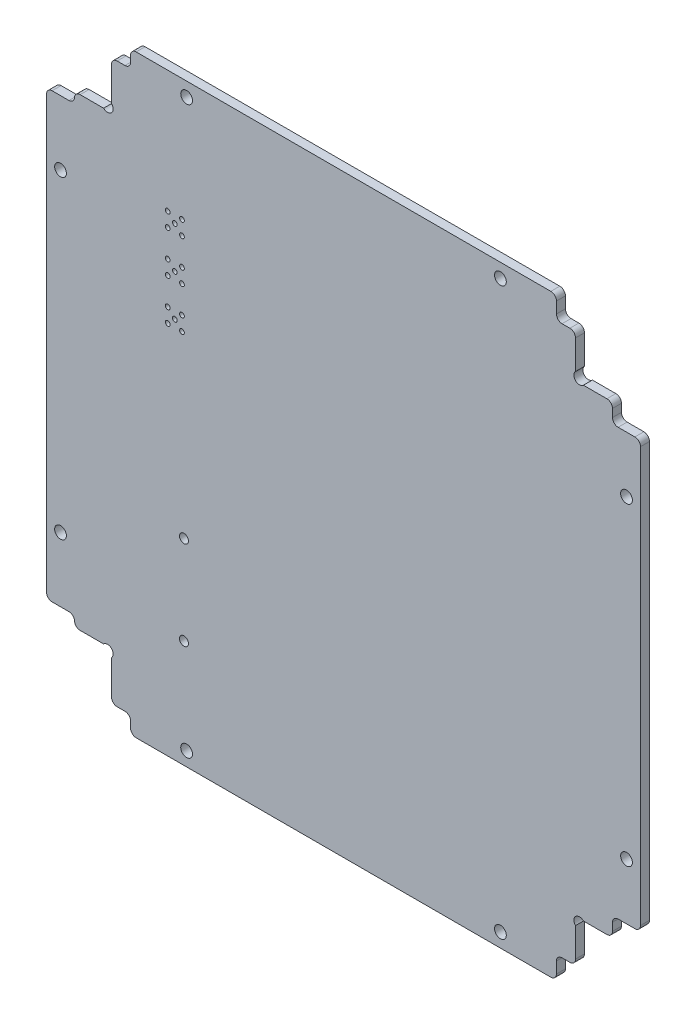
SolidWorks part; units mm, degrees
ref_plane "Front Plane" through (0, 0, 0) normal (0, 0, 1) x (1, 0, 0)
ref_plane "Top Plane" through (0, 0, 0) normal (0, 1, 0) x (1, 0, 0)
ref_plane "Right Plane" through (0, 0, 0) normal (1, 0, 0) x (0, 0, -1)
sketch "Sketch1" plane through (0, 0, 0) normal (0, 0, 1) x (1, 0, 0)
  line L0 (53, 53) -> (-53, -53) construction
  line L1 (53, 53) -> (-53, 53)
  line L2 (53, 53) -> (53, -53)
  line L3 (53, -53) -> (-53, -53)
  line L4 (-53, 53) -> (-53, -53)
  point P4 (0, 0)
  dimension "D1" = 106
  dimension "D2" = 106
extrude "mainOutline" add sketch "Sketch1" along normal blind 1.6
sketch "axisLabels" plane through (0, 0, 0) normal (0, 0, -1) x (-1, 0, 0)
  text T0 "+Y"
  text T1 "+X"
sketch "Sketch4" plane through (0, 0, 0) normal (0, 0, -1) x (-1, 0, 0)
  line L1 (-41.4, -41.4) -> (-48, -41.4)
  line L3 (-41.4, -49) -> (-41.4, -41.4)
  line L5 (-60.1065, -39) -> (-49.9975, -39)
  line L7 (-39, -61.4521) -> (-39, -49.9)
  line L9 (39, -56.2753) -> (39, -49.9)
  line L10 (-53, 53) -> (53, 53) construction
  line L11 (41.4, -49.9) -> (41.4, -41.4)
  line L12 (-53, -53) -> (-53, 53) construction
  line L13 (41.4, -41.4) -> (48, -41.4)
  line L15 (48, -40.5) -> (55.5177, -40.5)
  line L17 (55.3838, 40.5) -> (48, 40.5)
  line L19 (39, 57.6877) -> (39, 49.9)
  line L21 (-39, 59.8804) -> (-39, 49.9)
  line L23 (-56.8428, 39) -> (-49.9975, 39)
  line L25 (-41.4, 41.4) -> (-41.4, 49)
  line L27 (-48, 41.4) -> (-41.4, 41.4)
  line L29 (41.4, 49.9) -> (41.4, 41.4)
  line L31 (48, 41.4) -> (41.4, 41.4)
  line L32 (-48, 41.4) -> (-48, 39)
  line L33 (-48, 39) -> (-49.9975, 39)
  line L34 (-41.4, 49) -> (-39, 49)
  line L35 (-39, 49) -> (-39, 49.9)
  line L36 (48, 40.5) -> (48, 41.4)
  line L37 (39, 49.9) -> (41.4, 49.9)
  line L38 (48, -40.5) -> (48, -41.4)
  line L39 (39, -49.9) -> (41.4, -49.9)
  line L40 (-41.4, -49) -> (-39, -49)
  line L41 (-39, -49) -> (-39, -49.9)
  line L42 (-49.9975, -39) -> (-48, -39)
  line L43 (-48, -39) -> (-48, -41.4)
  line L44 (-39, 59.8804) -> (-56.8428, 59.8804)
  line L45 (-56.8428, 59.8804) -> (-56.8428, 39)
  line L46 (53, 53) -> (53, -53) construction
  line L47 (-60.1065, -39) -> (-60.1065, -61.4521)
  line L48 (-60.1065, -61.4521) -> (-39, -61.4521)
  line L49 (39, -56.2753) -> (55.5177, -56.2753)
  line L50 (55.5177, -56.2753) -> (55.5177, -40.5)
  line L51 (55.3838, 40.5) -> (55.3838, 57.6877)
  line L52 (55.3838, 57.6877) -> (39, 57.6877)
  line L53 (53, -53) -> (-53, -53) construction
  dimension "D1" = 14
  dimension "D2" = 11.6
  dimension "D3" = 5
  dimension "D4" = 12.5
  dimension "D5" = 11.6
  dimension "D6" = 3.1
  dimension "D7" = 12.5
  dimension "D8" = 14
  dimension "D9" = 3.1
  dimension "D10" = 5
  dimension "D11" = 11.6
  dimension "D12" = 11.6
  dimension "D13" = 14
  dimension "D14" = 14
  dimension "D15" = 11.6
  dimension "D16" = 11.6
  dimension "D17" = 5
  dimension "D18" = 4
  dimension "D19" = 14
  dimension "D20" = 14
  dimension "D21" = 11.6
  dimension "D22" = 11.6
  dimension "D23" = 4
  dimension "D24" = 5
extrude "railCutouts" cut sketch "Sketch4" against normal through all
sketch "Sketch5" plane through (0, 0, 0) normal (0, 0, -1) x (-1, 0, 0)
  line L0 (-48.7071, -39.7071) -> (-52.4015, -43.4015) construction
  line L1 (-48, -40.4142) -> (-51.6944, -44.1086) construction
  line L2 (-49.4142, -39) -> (-53.1086, -42.6944) construction
  line L3 (-48, -41.4) -> (-48, -39) construction
  line L4 (-48, 39) -> (-48, 41.4) construction
  line L5 (-42.1071, -42.1071) -> (-45.4445, -45.4445) construction
  line L6 (-41.4, -42.8142) -> (-44.7374, -46.1516)
  line L7 (-42.8142, -41.4) -> (-46.1516, -44.7374)
  line L8 (-39.7071, -49.7071) -> (-42.6199, -52.6199) construction
  line L9 (-39, -50.4142) -> (-41.9128, -53.327) construction
  line L10 (-40.4142, -49) -> (-43.327, -51.9128) construction
  line L11 (39.7071, -50.6071) -> (41.4231, -52.3231) construction
  line L12 (40.4142, -49.9) -> (42.1302, -51.616) construction
  line L13 (39, -51.3142) -> (40.716, -53.0302) construction
  line L14 (42.1071, -42.1071) -> (44.0402, -44.0402) construction
  line L15 (42.8142, -41.4) -> (44.7473, -43.3331)
  line L16 (41.4, -42.8142) -> (43.3331, -44.7473)
  line L17 (48.7071, -41.2071) -> (49.9793, -42.4793) construction
  line L18 (49.4142, -40.5) -> (50.6865, -41.7722) construction
  line L19 (48, -41.9142) -> (49.2722, -43.1865) construction
  line L20 (48.7071, 41.2071) -> (50.5001, 43.0001) construction
  line L21 (48, 41.9142) -> (49.793, 43.7072) construction
  line L22 (49.4142, 40.5) -> (51.2072, 42.293) construction
  line L23 (42.1071, 42.1071) -> (44.029, 44.029) construction
  line L24 (41.4, 42.8142) -> (43.3219, 44.7361)
  line L25 (42.8142, 41.4) -> (44.7361, 43.3219)
  line L26 (39.7071, 50.6071) -> (41.2638, 52.1638) construction
  line L27 (39, 51.3142) -> (40.5567, 52.8709) construction
  line L28 (40.4142, 49.9) -> (41.9709, 51.4567) construction
  line L29 (-48.7071, 39.7071) -> (-50.0606, 41.0606) construction
  line L30 (-49.4142, 39) -> (-50.7677, 40.3535) construction
  line L31 (-48, 40.4142) -> (-49.3535, 41.7677) construction
  line L32 (-42.1071, 42.1071) -> (-43.7968, 43.7968) construction
  line L33 (-42.8142, 41.4) -> (-44.5039, 43.0897)
  line L34 (-41.4, 42.8142) -> (-43.0897, 44.5039)
  line L35 (-39.7071, 49.7071) -> (-41.256, 51.256) construction
  line L36 (-40.4142, 49) -> (-41.9631, 50.5489) construction
  line L37 (-39, 50.4142) -> (-40.5489, 51.9631) construction
  line L38 (-41.4, 41.4) -> (-41.4, 49) construction
  line L39 (-39, 49) -> (-39, 53) construction
  line L40 (39, 53) -> (39, 49.9) construction
  line L41 (41.4, 49.9) -> (41.4, 41.4) construction
  line L42 (48, 41.4) -> (48, 40.5) construction
  line L43 (39, -49.9) -> (39, -53) construction
  line L44 (41.4, -41.4) -> (41.4, -49.9) construction
  line L45 (53, -40.5) -> (48, -40.5) construction
  line L46 (-39, -53) -> (-39, -49) construction
  line L47 (-41.4, -49) -> (-41.4, -41.4) construction
  arc A0 (-48, -40.4142) -> (-49.4142, -39) centre (-48.7071, -39.7071) ccw construction
  arc A1 (-53.1086, -42.6944) -> (-51.6944, -44.1086) centre (-52.4015, -43.4015) ccw construction
  arc A2 (-41.4, -42.8142) -> (-42.8142, -41.4) centre (-42.1071, -42.1071) ccw
  arc A3 (-46.1516, -44.7374) -> (-44.7374, -46.1516) centre (-45.4445, -45.4445) ccw
  arc A4 (-39, -50.4142) -> (-40.4142, -49) centre (-39.7071, -49.7071) ccw construction
  arc A5 (-43.327, -51.9128) -> (-41.9128, -53.327) centre (-42.6199, -52.6199) ccw construction
  arc A6 (40.4142, -49.9) -> (39, -51.3142) centre (39.7071, -50.6071) ccw construction
  arc A7 (40.716, -53.0302) -> (42.1302, -51.616) centre (41.4231, -52.3231) ccw construction
  arc A8 (42.8142, -41.4) -> (41.4, -42.8142) centre (42.1071, -42.1071) ccw
  arc A9 (43.3331, -44.7473) -> (44.7473, -43.3331) centre (44.0402, -44.0402) ccw
  arc A10 (49.4142, -40.5) -> (48, -41.9142) centre (48.7071, -41.2071) ccw construction
  arc A11 (49.2722, -43.1865) -> (50.6865, -41.7722) centre (49.9793, -42.4793) ccw construction
  arc A12 (48, 41.9142) -> (49.4142, 40.5) centre (48.7071, 41.2071) ccw construction
  arc A13 (51.2072, 42.293) -> (49.793, 43.7072) centre (50.5001, 43.0001) ccw construction
  arc A14 (41.4, 42.8142) -> (42.8142, 41.4) centre (42.1071, 42.1071) ccw
  arc A15 (44.7361, 43.3219) -> (43.3219, 44.7361) centre (44.029, 44.029) ccw
  arc A16 (39, 51.3142) -> (40.4142, 49.9) centre (39.7071, 50.6071) ccw construction
  arc A17 (41.9709, 51.4567) -> (40.5567, 52.8709) centre (41.2638, 52.1638) ccw construction
  arc A18 (-49.4142, 39) -> (-48, 40.4142) centre (-48.7071, 39.7071) ccw construction
  arc A19 (-49.3535, 41.7677) -> (-50.7677, 40.3535) centre (-50.0606, 41.0606) ccw construction
  arc A20 (-42.8142, 41.4) -> (-41.4, 42.8142) centre (-42.1071, 42.1071) ccw
  arc A21 (-43.0897, 44.5039) -> (-44.5039, 43.0897) centre (-43.7968, 43.7968) ccw
  arc A22 (-40.4142, 49) -> (-39, 50.4142) centre (-39.7071, 49.7071) ccw construction
  arc A23 (-40.5489, 51.9631) -> (-41.9631, 50.5489) centre (-41.256, 51.256) ccw construction
  point P2 (-50.5543, -41.5543)
  point P9 (-43.7758, -43.7758)
  point P17 (-41.1635, -51.1635)
  point P24 (40.5651, -51.4651)
  point P31 (43.0736, -43.0736)
  point P38 (49.3432, -41.8432)
  point P45 (49.6036, 42.1036)
  point P52 (43.0681, 43.0681)
  point P59 (40.4855, 51.3855)
  point P66 (-49.3839, 40.3839)
  point P73 (-42.952, 42.952)
  point P80 (-40.4815, 50.4815)
  dimension "D2" = 1
  dimension "D1" = 45
  dimension "D3" = 45
  dimension "D4" = 45
  dimension "D5" = 45
  dimension "D6" = 45
  dimension "D7" = 45
  dimension "D8" = 45
  dimension "D9" = 45
  dimension "D10" = 45
  dimension "D11" = 45
  dimension "D12" = 45
  dimension "D13" = 45
extrude "dogbones" cut sketch "Sketch5" against normal through all
sketch "Sketch6" plane through (0, 0, 0) normal (0, 0, -1) x (-1, 0, 0)
  line L0 (-39, 50) -> (-39, 53) construction
  line L1 (-39, 49) -> (-39, 53) construction
  line L2 (-39, 53) -> (39, 53) construction
  line L3 (-40, 50) -> (-40, 53)
  line L4 (-38, 50) -> (-38, 53)
  line L5 (-49, 39) -> (-53, 39) construction
  line L6 (-53, 39) -> (-48, 39) construction
  line L7 (-49, 38) -> (-53, 38)
  line L8 (-49, 40) -> (-53, 40)
  line L9 (-49, -39) -> (-55.2142, -39) construction
  line L10 (-48, -39) -> (-53, -39) construction
  line L11 (-49, -40) -> (-55.2142, -40)
  line L12 (-49, -38) -> (-55.2142, -38)
  line L13 (-39, -50) -> (-39, -53.9161) construction
  line L14 (-39, -53) -> (-39, -49) construction
  line L15 (-38, -50) -> (-38, -53.9161)
  line L16 (-40, -50) -> (-40, -53.9161)
  line L17 (39, -50.9) -> (39, -54.538) construction
  line L18 (39, -49.9) -> (39, -53) construction
  line L19 (40, -50.9) -> (40, -54.538)
  line L20 (38, -50.9) -> (38, -54.538)
  line L21 (49, -40.5) -> (54.2026, -40.5) construction
  line L22 (53, -40.5) -> (48, -40.5) construction
  line L23 (49, -39.5) -> (54.2026, -39.5)
  line L24 (49, -41.5) -> (54.2026, -41.5)
  line L25 (49, 40.5) -> (54.5566, 40.5) construction
  line L26 (48, 40.5) -> (53, 40.5) construction
  line L27 (49, 41.5) -> (54.5566, 41.5)
  line L28 (49, 39.5) -> (54.5566, 39.5)
  line L29 (39, 50.9) -> (39, 55.8281) construction
  line L30 (39, 53) -> (39, 49.9) construction
  line L31 (38, 50.9) -> (38, 55.8281)
  line L32 (40, 50.9) -> (40, 55.8281)
  line L33 (-48, -41.4) -> (-48, -39) construction
  line L34 (-39, -49) -> (-41.4, -49) construction
  line L35 (41.4, -49.9) -> (39, -49.9) construction
  line L36 (48, -40.5) -> (48, -41.4) construction
  line L37 (48, 41.4) -> (48, 40.5) construction
  line L38 (39, 49.9) -> (41.4, 49.9) construction
  arc A0 (-40, 50) -> (-38, 50) centre (-39, 50) ccw
  arc A1 (-38, 53) -> (-40, 53) centre (-39, 53) ccw
  arc A2 (-49, 38) -> (-49, 40) centre (-49, 39) ccw
  arc A3 (-53, 40) -> (-53, 38) centre (-53, 39) ccw
  arc A4 (-49, -40) -> (-49, -38) centre (-49, -39) ccw
  arc A5 (-55.2142, -38) -> (-55.2142, -40) centre (-55.2142, -39) ccw
  arc A6 (-38, -50) -> (-40, -50) centre (-39, -50) ccw
  arc A7 (-40, -53.9161) -> (-38, -53.9161) centre (-39, -53.9161) ccw
  arc A8 (40, -50.9) -> (38, -50.9) centre (39, -50.9) ccw
  arc A9 (38, -54.538) -> (40, -54.538) centre (39, -54.538) ccw
  arc A10 (49, -39.5) -> (49, -41.5) centre (49, -40.5) ccw
  arc A11 (54.2026, -41.5) -> (54.2026, -39.5) centre (54.2026, -40.5) ccw
  arc A12 (49, 41.5) -> (49, 39.5) centre (49, 40.5) ccw
  arc A13 (54.5566, 39.5) -> (54.5566, 41.5) centre (54.5566, 40.5) ccw
  arc A14 (38, 50.9) -> (40, 50.9) centre (39, 50.9) ccw
  arc A15 (40, 55.8281) -> (38, 55.8281) centre (39, 55.8281) ccw
  point P6 (-39, 51.5)
  point P11 (-51, 39)
  point P21 (-52.1071, -39)
  point P30 (-39, -51.958)
  point P39 (39, -52.719)
  point P48 (51.6013, -40.5)
  point P57 (51.7783, 40.5)
  point P66 (39, 53.364)
  point P75 (-39, 49)
  dimension "D1" = 1
extrude "solarFillets" cut sketch "Sketch6" against normal through all
fillet "handlingFillets" radius 1 16 edges at (-41.4, -49.9, 0.8) (-38, -53, 0.8) (-53, -39.5, 0.8) (-48, -41.4, 0.8) (-48, 41.4, 0.8) (-53, 39.5, 0.8) (-41.4, 49.9, 0.8) (-38, 53, 0.8) (38, 53, 0.8) (41.4, 49, 0.8) (48, 41.4, 0.8) (53, 38, 0.8) (53, -38, 0.8) (48, -41.4, 0.8) (41.4, -49, 0.8) (38, -53, 0.8)
sketch "Sketch7" plane through (0, 0, 1.6) normal (0, 0, 1) x (1, 0, 0)
  line L0 (-37, -53) -> (37, -53) construction
  line L1 (-53, 38.5) -> (-53, -38.5) construction
  line L2 (37, 53) -> (-37, 53) construction
  line L3 (-31.37, 28.67) -> (-31.37, 31.21) construction
  line L4 (-31.37, 31.21) -> (-28.83, 31.21) construction
  line L5 (-28.83, 31.21) -> (-28.83, 28.67) construction
  line L6 (-28.83, 28.67) -> (-31.37, 28.67) construction
  line L7 (-31.37, 28.67) -> (-28.83, 31.21) construction
  circle A1 centre (-28.4723, -17.925) radius 0.8
  circle A3 centre (-28.4723, -33.775) radius 0.8
  circle A5 centre (-31.37, 28.67) radius 0.425
  circle A7 centre (-28.83, 28.67) radius 0.425
  circle A9 centre (-30.1, 29.94) radius 0.425
  circle A10 centre (-28.83, 31.21) radius 0.425
  circle A11 centre (-31.37, 31.21) radius 0.425
  circle A12 centre (-31.37, 21.27) radius 0.425
  circle A13 centre (-28.83, 21.27) radius 0.425
  circle A14 centre (-30.1, 22.54) radius 0.425
  circle A15 centre (-28.83, 23.81) radius 0.425
  circle A16 centre (-31.37, 23.81) radius 0.425
  circle A17 centre (-31.37, 13.87) radius 0.425
  circle A18 centre (-28.83, 13.87) radius 0.425
  circle A19 centre (-30.1, 15.14) radius 0.425
  circle A20 centre (-28.83, 16.41) radius 0.425
  circle A21 centre (-31.37, 16.41) radius 0.425
  point P13 (-30.1, 29.94)
  point P21 (0, 0)
  dimension "D8" = 1.6
  dimension "D9" = 3
  dimension "D6" = 0.85
  dimension "D1" = 19.225
  dimension "D2" = 24.5277
  dimension "D3" = 15.85
  dimension "D4" = 23.06
  dimension "D5" = 22.9
  dimension "D7" = 2.54
  dimension "D10" = 7.4
extrude "connectorHoles" cut sketch "Sketch7" against normal through all
hole_wizard "M2 Clearance Hole1" positions "Sketch8" profile "Sketch9" hole size "M2" standard "ANSI Metric" end condition through all
sketch "Sketch8" plane through (0, 0, 0) normal (0, 0, -1) x (-1, 0, 0)
  line L0 (53, 38.5) -> (53, -38.5) construction
  line L1 (37, -53) -> (-37, -53) construction
  line L2 (-53, -37) -> (-53, 37) construction
  line L3 (53, 0) -> (-53, 0) construction
  line L5 (0, -53) -> (0, -11.6379) construction
  point P0 (50.5, -28)
  point P1 (28, -50.5)
  point P5 (-50.5, -28)
  point P29 (0, 0)
  point P30 (-28, -50.5)
  point P31 (-28, 50.5)
  point P32 (-50.5, 28)
  point P33 (28, 50.5)
  point P34 (50.5, 28)
  dimension "D1" = 2.5
  dimension "D2" = 2.5
  dimension "D4" = 2.5
  dimension "D5" = 25
  dimension "D6" = 25
  dimension "D7" = 25
sketch "Sketch9" plane through (-50.5, -28, 0) normal (1, 0, 0) x (0, 1, 0)
  line L0 (0, 0) -> (0, 1.6)
  line L1 (0, 1.6) -> (1.05, 1.6)
  line L2 (1.05, 1.6) -> (1.05, 0)
  line L5 (1.05, 0) -> (0, 0)
  line L11 (0, -6.35) -> (0, 107.95) construction
  dimension "Thru Hole Dia." = 2.1
  dimension "Thru Hole Depth" = 1.6
